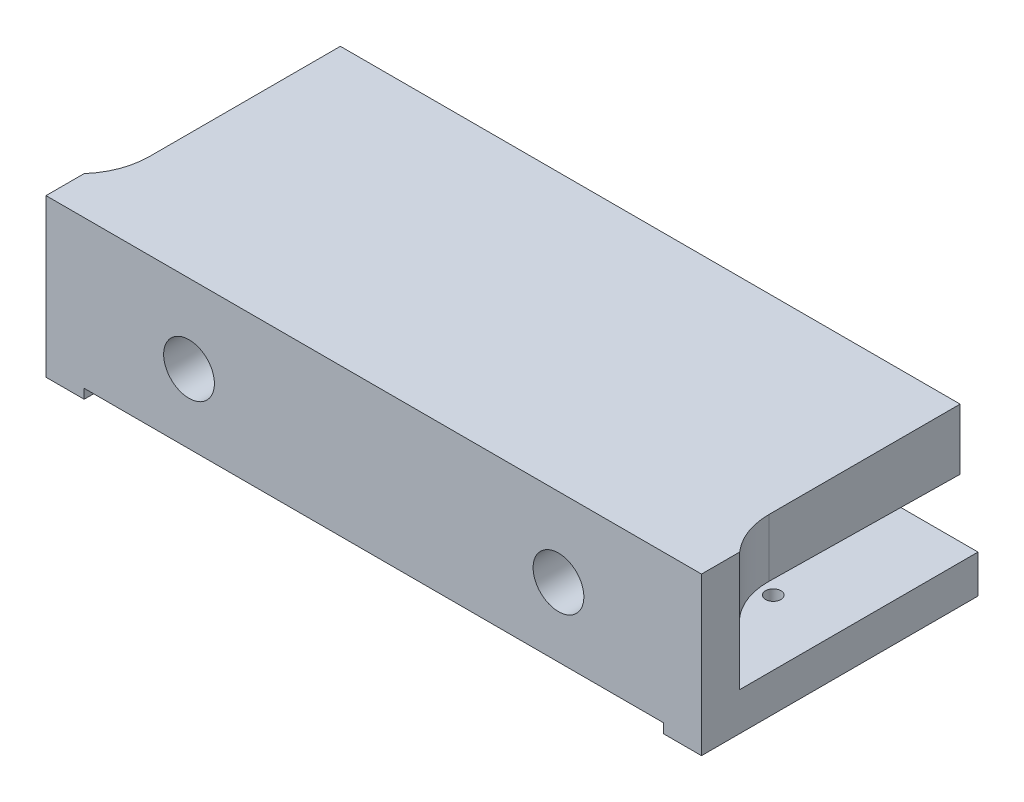
SolidWorks part; units mm, degrees
ref_plane "Front Plane" through (0, 0, 0) normal (0, 0, 1) x (1, 0, 0)
ref_plane "Top Plane" through (0, 0, 0) normal (0, 1, 0) x (1, 0, 0)
ref_plane "Right Plane" through (0, 0, 0) normal (1, 0, 0) x (0, 0, -1)
sketch "Sketch1" plane through (0, 0, 0) normal (0, 1, 0) x (1, 0, 0)
  line L1 (-34.925, -14.732) -> (34.925, -14.732)
  line L2 (-34.925, -14.732) -> (-34.925, 14.732)
  line L3 (-34.925, 14.732) -> (34.925, 14.732)
  line L4 (34.925, -14.732) -> (34.925, 14.732)
  line L5 (-34.925, -14.732) -> (34.925, 14.732) construction
  line L6 (-34.925, 14.732) -> (34.925, -14.732) construction
  point P0 (0, 0)
  dimension "D1" = 29.464
  dimension "D2" = 69.85
extrude "Boss-Extrude1" add sketch "Sketch1" along normal blind 16.764
sketch "Sketch2" plane through (-34.925, 0, 0) normal (-1, 0, 0) x (0, 0, 1)
  line L0 (-14.732, 16.764) -> (-14.732, 0) construction
  line L1 (-14.732, 10.414) -> (10.668, 10.414)
  line L2 (-14.732, 10.414) -> (-14.732, 4.064)
  line L3 (-14.732, 4.064) -> (10.668, 4.064)
  line L4 (10.668, 10.414) -> (10.668, 4.064)
  dimension "D1" = 6.35
  dimension "D2" = 25.4
  dimension "D3" = 4.064
extrude "Cut-Extrude1" cut sketch "Sketch2" against normal up to surface (69.85 mm away) up to face at (34.925, 8.382, 0)
sketch "Sketch3" plane through (-34.925, 0, 0) normal (-1, 0, 0) x (0, 0, 1)
  line L0 (10.668, 10.414) -> (-14.732, 10.414) construction
  line L1 (-14.732, 16.764) -> (10.668, 16.764)
  line L2 (-14.732, 16.764) -> (-14.732, 10.414)
  line L3 (-14.732, 10.414) -> (10.668, 10.414)
  line L4 (10.668, 16.764) -> (10.668, 10.414)
  dimension "D1" = 25.4
extrude "Cut-Extrude2" cut sketch "Sketch3" against normal blind 50.8
mirror "Mirror1" about plane through (0, 0, 0) normal (1, 0, 0) of "Cut-Extrude2"
sketch "Sketch5" plane through (0, 0, 0) normal (0, -1, 0) x (1, 0, 0)
  line L0 (-27.9908, 0.1524) -> (27.9908, 0.1524) construction
  line L1 (-34.925, 14.732) -> (34.925, 14.732) construction
  line L3 (-30.861, 14.732) -> (30.861, 14.732)
  line L4 (-30.861, 14.732) -> (-30.861, -2.3876)
  line L5 (-30.861, -2.3876) -> (30.861, -2.3876)
  line L6 (30.861, 14.732) -> (30.861, -2.3876)
  circle A0 centre (-27.9908, 0.1524) radius 0.8192
  circle A1 centre (27.9908, 0.1524) radius 0.8192
  point P0 (-27.9908, 0.1524)
  point P1 (27.9908, 0.1524)
  point P2 (0, 0.1524)
  point P12 (0, -2.3876)
  point P18 (0, -2.3876)
  line M3 (34.925, 14.732) -> (-34.925, 14.732)
  dimension "D5" = 1.6383
  dimension "D6" = 1.6383
  dimension "D1" = 2.54
  dimension "D2" = 55.9816
  dimension "D3" = 17.1196
  dimension "D4" = 61.722
extrude "Cut-Extrude3" cut sketch "Sketch5" against normal blind 1.016 contours L6 L4 L5 A0 A1 M3 | A0 | A1 region at (0, 0, 6.1963) region at (-27.9908, 0, 0.1524) region at (27.9908, 0, 0.1524)
extrude "Cut-Extrude4" cut sketch "Sketch5<3>" against normal through all contours A0 | A1 region at (-27.9908, 0, 0.1524) region at (27.9908, 0, 0.1524)
sketch "Sketch5<3>" plane through (0, 0, 0) normal (0, -1, 0) x (1, 0, 0) same geometry as "Sketch5"
sketch "Sketch7" plane through (0, 0, 10.668) normal (0, 0, -1) x (-1, 0, 0)
  line L0 (-34.925, 16.764) -> (34.925, 16.764) construction
  line L1 (-34.925, 9.144) -> (34.925, 9.144)
  line L2 (-34.925, 9.144) -> (-34.925, 16.764)
  line L3 (-34.925, 16.764) -> (34.925, 16.764)
  line L4 (34.925, 9.144) -> (34.925, 16.764)
  line L5 (-34.925, 9.144) -> (34.925, 16.764) construction
  line L6 (-34.925, 16.764) -> (34.925, 9.144) construction
  line L7 (-34.925, 4.064) -> (34.925, 4.064) construction
  point P0 (0, 12.954)
  dimension "D1" = 5.08
  dimension "D2" = 69.85
extrude "Boss-Extrude2" add sketch "Sketch7" along normal blind 25.4
sketch "Sketch8" plane through (-34.925, 0, 0) normal (-1, 0, 0) x (0, 0, 1)
  line L0 (-14.732, 10.287) -> (10.668, 10.668)
  line L1 (-14.732, 9.144) -> (-14.732, 16.764) construction
  line L3 (-14.732, 9.144) -> (10.668, 9.144) construction
  line L5 (10.668, 9.144) -> (10.668, 4.064) construction
  line L6 (-14.732, 10.287) -> (-14.732, 9.144)
  line L7 (-14.732, 9.144) -> (10.668, 9.144)
  line L8 (10.668, 9.144) -> (10.668, 10.668)
  dimension "D1" = 1.143
  dimension "D2" = 1.524
extrude "Cut-Extrude9" cut sketch "Sketch8" against normal through all both and the other way through all
sketch "Sketch13" plane through (0, 0, 14.732) normal (0, 0, 1) x (1, 0, 0)
  line L0 (-19.685, 8.382) -> (19.685, 8.382) construction
  line L2 (34.925, 16.764) -> (-34.925, 0) construction
  circle A0 centre (-19.685, 8.382) radius 2.7051
  circle A1 centre (19.685, 8.382) radius 2.7051
  point P4 (0, 8.382)
  point P5 (0, 8.382)
  dimension "D2" = 5.4102
  dimension "D3" = 5.4102
  dimension "D1" = 39.37
extrude "Cut-Extrude12" cut sketch "Sketch13" against normal blind 4.064
sketch "Sketch16" plane through (0, 0, 14.732) normal (0, 0, 1) x (1, 0, 0)
  line L0 (-13.4811, 16.764) -> (13.4811, 16.764)
  line L1 (-13.4811, 16.764) -> (-13.481, 2.1717)
  line L2 (-13.481, 2.1717) -> (13.481, 2.1717)
  line L3 (13.4811, 16.764) -> (13.481, 2.1717)
  line L4 (-11.2459, 14.859) -> (12.3635, 14.859) construction
  line L5 (-11.2459, 14.859) -> (-11.2459, 7.8867) construction
  line L6 (-11.2459, 7.8867) -> (12.3635, 7.8867) construction
  line L7 (12.3635, 14.859) -> (12.3635, 7.8867) construction
  line L8 (13.4811, 16.764) -> (3.3211, 16.764)
  line L9 (13.4811, 16.764) -> (13.4811, 11.684)
  line L10 (13.4811, 11.684) -> (3.3211, 11.684)
  line L11 (3.3211, 16.764) -> (3.3211, 11.684)
  line L12 (-13.481, 2.1717) -> (-3.321, 2.1717)
  line L13 (-13.481, 2.1717) -> (-13.481, 9.1567)
  line L14 (-13.481, 9.1567) -> (-3.321, 9.1567)
  line L15 (-3.321, 2.1717) -> (-3.321, 9.1567)
  line L16 (-34.925, 16.764) -> (34.925, 16.764) construction
  circle A0 centre (-11.2459, 14.859) radius 0.8255
  circle A1 centre (12.3635, 14.859) radius 0.8255
  circle A2 centre (12.3635, 7.8867) radius 0.8255
  circle A3 centre (-11.2459, 7.8867) radius 0.8255
  point P18 (0, 16.764)
  point P21 (0, 16.764)
  dimension "D7" = 1.651
  dimension "D8" = 1.651
  dimension "D9" = 1.651
  dimension "D10" = 1.651
  dimension "D1" = 26.9621
  dimension "D2" = 14.5923
  dimension "D3" = 2.2352
  dimension "D4" = 1.1176
  dimension "D5" = 1.905
  dimension "D6" = 5.715
  dimension "D11" = 10.16
  dimension "D12" = 5.08
  dimension "D13" = 10.16
  dimension "D14" = 6.985
sketch "Sketch17" plane through (0, 0, -14.732) normal (0, 0, -1) x (-1, 0, 0)
  line L0 (34.925, 16.764) -> (-34.925, 16.764) construction
  line L1 (-33.02, 16.764) -> (33.02, 16.764)
  line L2 (-33.02, 16.764) -> (-33.02, 10.287)
  line L3 (-33.02, 10.287) -> (33.02, 10.287)
  line L4 (33.02, 16.764) -> (33.02, 10.287)
  line L5 (-34.925, 10.287) -> (34.925, 10.287) construction
  line L7 (-33.02, 16.764) -> (-34.925, 16.764)
  line L8 (-33.02, 16.764) -> (-33.02, 10.287)
  line L9 (-33.02, 10.287) -> (-34.925, 10.287)
  line L10 (-34.925, 16.764) -> (-34.925, 10.287)
  line L11 (33.02, 16.764) -> (34.925, 16.764)
  line L12 (33.02, 16.764) -> (33.02, 10.287)
  line L13 (33.02, 10.287) -> (34.925, 10.287)
  line L14 (34.925, 16.764) -> (34.925, 10.287)
  point P13 (0, 16.764)
  line M4 (-34.925, 16.764) -> (-34.925, 10.287)
  line M5 (-34.925, 10.287) -> (34.925, 10.287)
  line M6 (34.925, 10.287) -> (34.925, 16.764)
  line M7 (34.925, 16.764) -> (-34.925, 16.764)
  dimension "D1" = 66.04
extrude "Cut-Extrude13" cut sketch "Sketch17" against normal up to surface (25.4 mm away) contours L2 M7 M4 M5 | L4 M7 M5 M6 region at (33.9725, 13.5255, -14.732) region at (-33.9725, 13.5255, -14.732) up to face at (0, 7.7692, 10.668)
fillet "Fillet1" radius 7.62 2 edges at (-33.02, 13.716, 10.668) (33.02, 13.716, 10.668)
